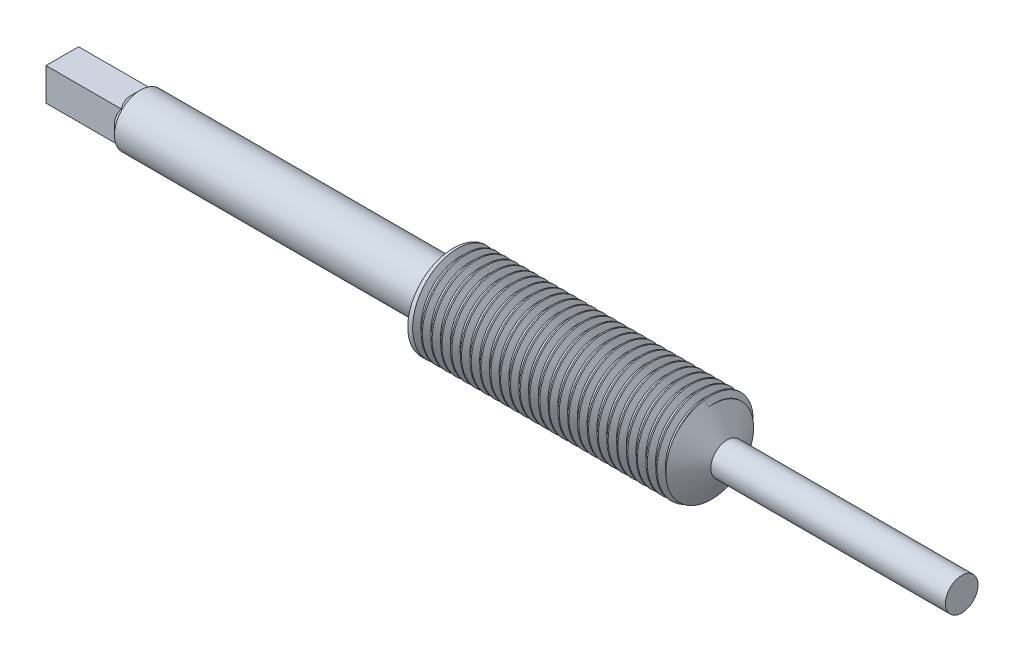
SolidWorks part; units mm, degrees
ref_plane "前视基准面" through (0, 0, 0) normal (0, 0, 1) x (1, 0, 0)
ref_plane "上视基准面" through (0, 0, 0) normal (0, 1, 0) x (1, 0, 0)
ref_plane "右视基准面" through (0, 0, 0) normal (1, 0, 0) x (0, 0, -1)
sketch "草图1" plane through (0, 0, 0) normal (0, 0, 1) x (1, 0, 0)
  line L0 (0, 0) -> (95.8472, 0) construction
  line L1 (-47.7243, 0) -> (-47.7243, 4)
  line L2 (-47.7243, 4) -> (2.2757, 4)
  line L3 (2.2757, 4) -> (2.2757, 7)
  line L4 (2.2757, 7) -> (41.6776, 7)
  line L5 (41.6776, 7) -> (44.2757, 2.5)
  line L6 (44.2757, 2.5) -> (80.2757, 2.5)
  line L7 (80.2757, 2.5) -> (80.2757, 0)
  line L8 (-47.7243, 0) -> (80.2757, 0)
  dimension "D1" = 60
  dimension "D2" = 4
  dimension "D3" = 50
  dimension "D4" = 5
  dimension "D5" = 14
  dimension "D6" = 36
  dimension "D7" = 128
revolve "旋转3" add sketch "草图1" angle 360 about L0
sketch "草图2" plane through (-47.7243, 0, 0) normal (-1, 0, 0) x (0, 0, 1)
  line L1 (-2.5, -2.5) -> (2.5, -2.5)
  line L2 (-2.5, -2.5) -> (-2.5, 2.5)
  line L3 (-2.5, 2.5) -> (2.5, 2.5)
  line L4 (2.5, -2.5) -> (2.5, 2.5)
  line L5 (-2.5, -2.5) -> (2.5, 2.5) construction
  line L6 (-2.5, 2.5) -> (2.5, -2.5) construction
  point P0 (0, 0)
  dimension "D1" = 5
  dimension "D2" = 5
extrude "凸台-拉伸1" add sketch "草图2" along normal blind 10
chamfer "倒角1" distance 2 angle 45 1 edges at (-47.7243, 0, 4)
thread "螺纹线1" pitch 1.5 method cut profile "螺纹线轮廓1" start angle 0, offset 0, length 42, pitch 1.5, diameter 14
ref_plane "基准面1" through (2.2757, 0, -7) normal (0, -1, 0) x (0, 0, -1)
sketch "螺纹线轮廓1" plane through (2.2757, 0, -7) normal (0, -1, 0) x (0, 0, -1)
  line L0 (0, 0) -> (0, 1.5) construction
  line L11 (0, 0) -> (0, 1.3125)
  line L12 (0, 1.3125) -> (-0.8119, 0.8437)
  line L13 (-0.8119, 0.8437) -> (-0.8119, 0.4687)
  line L15 (-0.8119, 0.4687) -> (0, 0)
  line L17 (-0.8119, 0.6562) -> (0, 0.6562) construction
  point P2 (0, 0)
  dimension "Pitch" = 1.5
  dimension "Profile_Angle" = 60
  dimension "Profile_Land" = 0.375
  dimension "Profile_Height" = 0.8119
